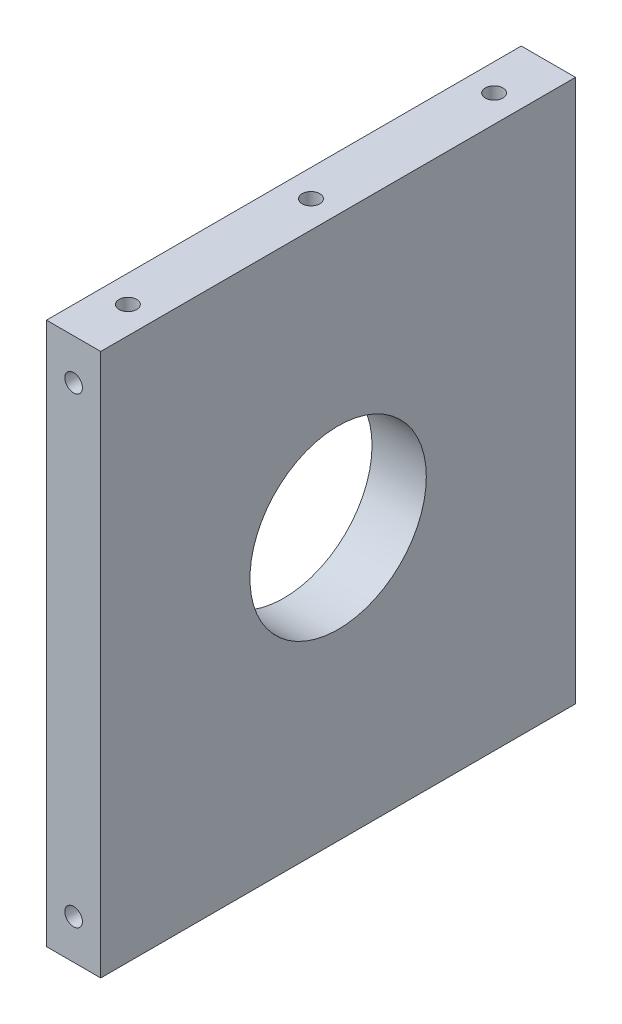
SolidWorks part; units mm, degrees
ref_plane "前视基准面" through (0, 0, 0) normal (0, 0, 1) x (1, 0, 0)
ref_plane "上视基准面" through (0, 0, 0) normal (0, 1, 0) x (1, 0, 0)
ref_plane "右视基准面" through (0, 0, 0) normal (1, 0, 0) x (0, 0, -1)
sketch "草图1" plane through (0, 0, 0) normal (1, 0, 0) x (0, 0, -1)
  line L1 (-35, 40) -> (35, 40)
  line L2 (-35, 40) -> (-35, -40)
  line L3 (-35, -40) -> (35, -40)
  line L4 (35, 40) -> (35, -40)
  line L5 (-35, 40) -> (35, -40) construction
  line L6 (-35, -40) -> (35, 40) construction
  point P0 (0, 0)
  dimension "D1" = 80
  dimension "D2" = 70
extrude "凸台-拉伸1" add sketch "草图1" along normal blind 8
sketch "草图4" plane through (8, 0, 0) normal (1, 0, 0) x (0, 0, -1)
  circle A0 centre (0, 0) radius 13
  dimension "D1" = 26
extrude "切除-拉伸2" cut sketch "草图4" against normal blind 8
sketch "草图5" plane through (0, 0, 35) normal (0, 0, 1) x (1, 0, 0)
  circle A0 centre (4, 34) radius 1.3
  circle A1 centre (4, -34.1568) radius 1.3
  dimension "D1" = 2.6
  dimension "D2" = 2.6
extrude "切除-拉伸3" cut sketch "草图5" against normal blind 10
mirror "镜向1" about plane through (0, 0, 0) normal (0, 0, 1) of "切除-拉伸3"
sketch "草图6" plane through (0, 40, 0) normal (0, 1, 0) x (1, 0, 0)
  line L0 (8, 35) -> (8, -35) construction
  line L1 (8, 35) -> (0, 35) construction
  line L2 (8, -35) -> (0, -35) construction
  circle A0 centre (4, 27) radius 1.3
  circle A1 centre (4, -27) radius 1.3
  circle A2 centre (4, 0) radius 1.3
  dimension "D1" = 2.6
  dimension "D2" = 4
  dimension "D3" = 4
  dimension "D4" = 4
  dimension "D5" = 8
  dimension "D6" = 8
  dimension "D7" = 35
extrude "切除-拉伸4" cut sketch "草图6" against normal blind 10
mirror "镜向2" about plane through (0, 0, 0) normal (0, 1, 0) of "切除-拉伸4"
